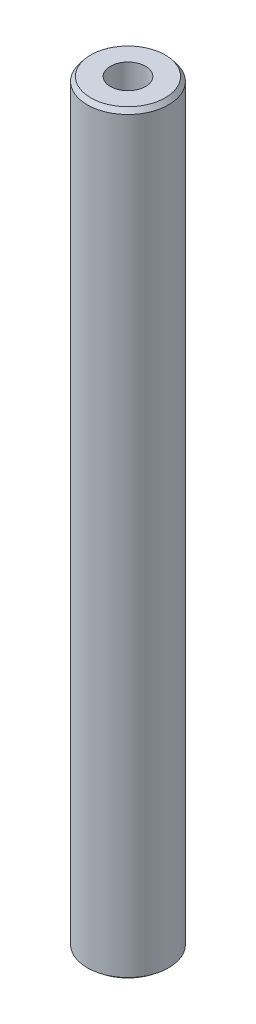
SolidWorks part; units mm, degrees
ref_plane "Front Plane" through (0, 0, 0) normal (0, 0, 1) x (1, 0, 0)
ref_plane "Top Plane" through (0, 0, 0) normal (0, 1, 0) x (1, 0, 0)
ref_plane "Right Plane" through (0, 0, 0) normal (1, 0, 0) x (0, 0, -1)
sketch "Sketch1" plane through (0, 0, 0) normal (0, 1, 0) x (1, 0, 0)
  circle A0 centre (0, 0) radius 25
  dimension "SHAFT_OD" = 50
extrude "Boss-Extrude1" add sketch "Sketch1" along normal blind 464.6043
sketch "Sketch2" plane through (0, 0, 0) normal (0, 1, 0) x (1, 0, 0)
  circle A0 centre (0, 0) radius 10.8218
  dimension "BORE_D" = 21.6436
extrude "Cut-Extrude1" cut sketch "Sketch2" along normal through all
chamfer "Chamfer1" distance 2.6718 angle 38.364 2 edges at (0, 464.6043, 25) (0, 0, 25) first distance on face at (0, 464.6043, 25) first distance on face at (0, 0, 10.8218)
